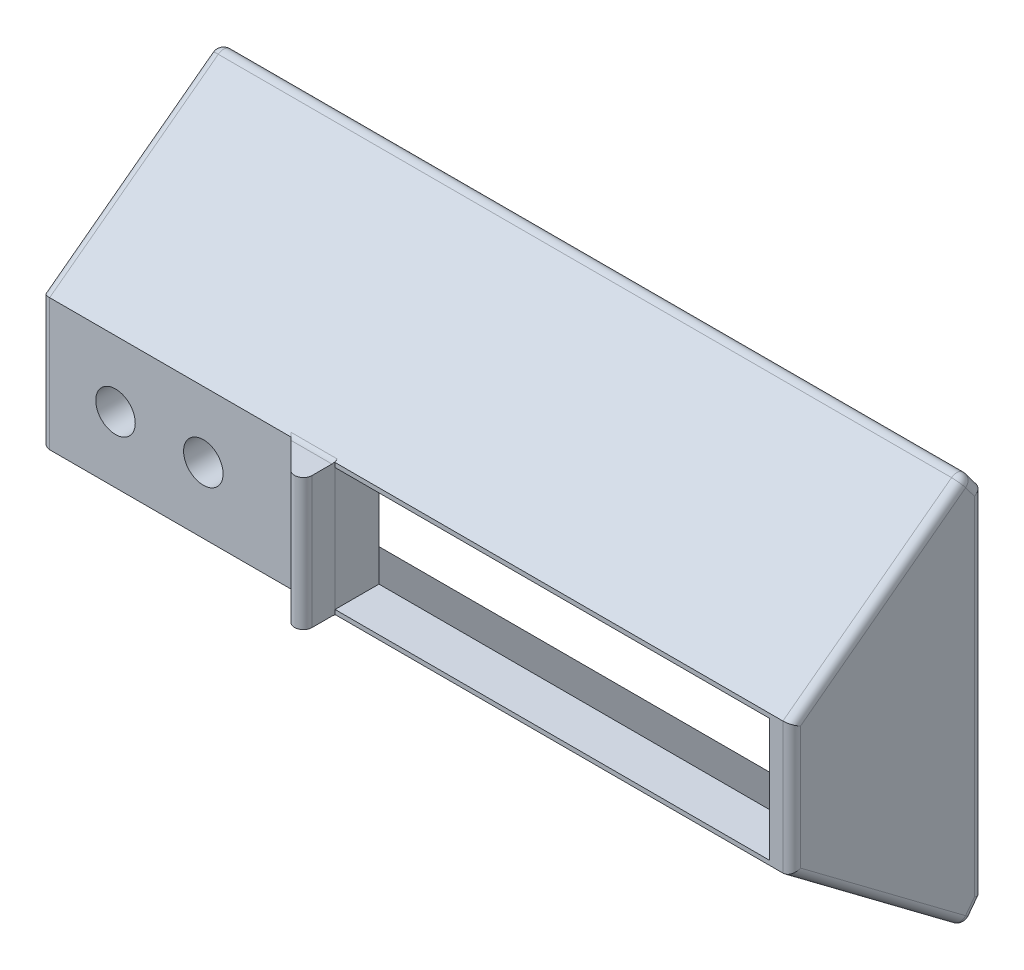
SolidWorks part; units mm, degrees
ref_plane "Front Plane" through (0, 0, 0) normal (1, 0, 0) x (0, 1, 0)
ref_plane "Top Plane" through (0, 0, 0) normal (0, 0, 1) x (0, 1, 0)
ref_plane "Right Plane" through (0, 0, 0) normal (0, 1, 0) x (-1, 0, 0)
sketch "Sketch1" plane through (0, 0, 0) normal (1, 0, 0) x (0, 1, 0)
  line L0 (-7.5, -2.5) -> (-20.1, -19.3)
  line L1 (-7.5, 2.5) -> (7.5, 2.5)
  line L2 (-7.5, 2.5) -> (-7.5, -2.5)
  line L3 (-7.5, -2.5) -> (7.5, -2.5)
  line L4 (7.5, 2.5) -> (7.5, -2.5)
  line L5 (-7.5, 2.5) -> (7.5, -2.5) construction
  line L6 (-7.5, -2.5) -> (7.5, 2.5) construction
  line L7 (-20.1, -19.3) -> (-22.5, -17.5)
  line L8 (-22.5, -17.5) -> (-7.5, 2.5)
  line L9 (0, -2.5) -> (0, 2.5) construction
  line L10 (22.5, -17.5) -> (7.5, 2.5)
  line L11 (20.1, -19.3) -> (22.5, -17.5)
  line L12 (7.5, -2.5) -> (20.1, -19.3)
  point P0 (0, 0)
  point P12 (0, 0)
  dimension "D1" = 20
  dimension "D2" = 15
  dimension "D3" = 5
  dimension "D4" = 15
extrude "Boss-Extrude1" add sketch "Sketch1" along normal blind 80 contours L8 L7 L0 L2 | L4 L1 L2 L3 | L4 L12 L11 L10 region at (0, -14.4174, -9.1507) region at (0, 0, 0) region at (0, 14.4174, -9.1507)
sketch "Sketch2" plane through (0, 0, 2.5) normal (0, 0, 1) x (1, 0, 0)
  line L0 (80, -7.5) -> (80, 7.5) construction
  line L1 (80, 7) -> (30.5, 7)
  line L2 (80, 7) -> (80, -7)
  line L3 (80, -7) -> (30.5, -7)
  line L4 (30.5, 7) -> (30.5, -7)
  line L5 (80, 7) -> (30.5, -7) construction
  line L6 (80, -7) -> (30.5, 7) construction
  line L7 (0, 0) -> (55.25, 0) construction
  line L8 (0, -7.5) -> (0, 7.5) construction
  circle A0 centre (5.5, 0) radius 2.25
  circle A1 centre (15.5, 0) radius 2.25
  point P4 (55.25, 0)
  dimension "D3" = 4.5
  dimension "D1" = 14
  dimension "D2" = 10
  dimension "D4" = 5.5
  dimension "D5" = 15
extrude "Cut-Extrude1" cut sketch "Sketch2" against normal through all
sketch "Sketch3" plane through (0, 0, 2.5) normal (0, 0, 1) x (1, 0, 0)
  line L0 (80, 7.5) -> (0, 7.5) construction
  line L1 (30.4776, 7.5) -> (22.4776, 7.5)
  line L2 (30.4776, 7.5) -> (30.4776, -7.5)
  line L3 (30.4776, -7.5) -> (22.4776, -7.5)
  line L4 (22.4776, 7.5) -> (22.4776, -7.5)
  line L5 (30.4776, 7.5) -> (22.4776, -7.5) construction
  line L6 (30.4776, -7.5) -> (22.4776, 7.5) construction
  line L7 (80, -7.5) -> (0, -7.5) construction
  point P4 (26.4776, 0)
  dimension "D1" = 8
extrude "Boss-Extrude2" add sketch "Sketch3" along normal blind 5
chamfer "Chamfer1" distance 8 angle 45 1 edges at (22.4776, 0, 7.5)
fillet "Fillet1" radius 1 5 edges at (40, -7.5, -2.5) (40, 7.5, -2.5) (27.9776, 7.5, 2.5) (27.9776, -7.5, 2.5) (30.4776, 0, 7.5)
sketch "Sketch4" plane through (0, 0, 0) normal (-1, 0, 0) x (0, -1, 0)
  line L8 (22.5, -17.5) -> (7.5, 2.5)
  line L9 (7.5, 2.5) -> (-7.5, 2.5)
  line L10 (-7.5, 2.5) -> (-22.5, -17.5)
  line L11 (-22.5, -17.5) -> (-20.1, -19.3)
  line L12 (-20.1, -19.3) -> (-7.8, -2.9)
  line L13 (-7, -2.5) -> (7, -2.5)
  line L14 (7.8, -2.9) -> (20.1, -19.3)
  line L15 (20.1, -19.3) -> (22.5, -17.5)
  line L16 (22.5, -17.5) -> (7.5, 2.5)
  line L17 (7.5, 2.5) -> (-7.5, 2.5)
  line L18 (-7.5, 2.5) -> (-22.5, -17.5)
  line L19 (-22.5, -17.5) -> (-20.1, -19.3)
  line L20 (-20.1, -19.3) -> (-7.8, -2.9)
  line L21 (-7, -2.5) -> (7, -2.5)
  line L22 (7.8, -2.9) -> (20.1, -19.3)
  line L23 (20.1, -19.3) -> (22.5, -17.5)
  arc A2 (-7, -2.5) -> (-7.8, -2.9) centre (-7, -3.5) ccw
  arc A3 (7.8, -2.9) -> (7, -2.5) centre (7, -3.5) ccw
  arc A4 (-7, -2.5) -> (-7.8, -2.9) centre (-7, -3.5) ccw
  arc A5 (7.8, -2.9) -> (7, -2.5) centre (7, -3.5) ccw
  dimension "D1" = 0
extrude "Boss-Extrude3" add sketch "Sketch4" along normal blind 3
sketch "Sketch6" plane through (80, 0, 0) normal (1, 0, 0) x (0, 1, 0)
  line L0 (7, 2.5) -> (7, -2.5) construction
  line L1 (7.8, -2.9) -> (20.1, -19.3) construction
  line L2 (20.1, -19.3) -> (22.5, -17.5) construction
  line L3 (22.5, -17.5) -> (7.5, 2.5) construction
  line L4 (7.5, 2.5) -> (7, 2.5) construction
  line L5 (-7, -2.5) -> (-7, 2.5) construction
  line L6 (-7, 2.5) -> (-7.5, 2.5) construction
  line L7 (-7.5, 2.5) -> (-22.5, -17.5) construction
  line L8 (-22.5, -17.5) -> (-20.1, -19.3) construction
  line L9 (-20.1, -19.3) -> (-7.8, -2.9) construction
  line L10 (7, 2.5) -> (7, -2.5)
  line L11 (7.8, -2.9) -> (20.1, -19.3)
  line L12 (20.1, -19.3) -> (22.5, -17.5)
  line L13 (22.5, -17.5) -> (7.5, 2.5)
  line L14 (7.5, 2.5) -> (7, 2.5)
  line L15 (-7, -2.5) -> (-7, 2.5)
  line L16 (-7, 2.5) -> (-7.5, 2.5)
  line L17 (-7.5, 2.5) -> (-22.5, -17.5)
  line L18 (-22.5, -17.5) -> (-20.1, -19.3)
  line L19 (-20.1, -19.3) -> (-7.8, -2.9)
  line L20 (-20.1, -19.3) -> (20.1, -19.3)
  line L21 (-7, 2.5) -> (7, 2.5)
  arc A0 (7.8, -2.9) -> (7, -2.5) centre (7, -3.5) ccw construction
  arc A1 (-7, -2.5) -> (-7.8, -2.9) centre (-7, -3.5) ccw construction
  arc A2 (7.8, -2.9) -> (7, -2.5) centre (7, -3.5) ccw
  arc A3 (-7, -2.5) -> (-7.8, -2.9) centre (-7, -3.5) ccw
  line M1 (7, 2.5) -> (7, -2.5)
  arc M2 (7, -2.5) -> (7.8, -2.9) centre (7, -3.5) cw
  line M3 (7.8, -2.9) -> (20.1, -19.3)
  line M4 (20.1, -19.3) -> (22.5, -17.5)
  line M5 (22.5, -17.5) -> (7.5, 2.5)
  line M6 (7.5, 2.5) -> (7, 2.5)
extrude "Boss-Extrude4" add sketch "Sketch6" along normal blind 2.5 contours L15 A3 L19 L20 L21 M3 M2 M1 | A3 L15 L16 L17 L18 L19 | M6 M1 M2 M3 M4 M5 region at (80, 14.1634, -8.8276) region at (80, 0, -10.582) region at (80, -14.1634, -8.8276)
fillet "Fillet3" radius 1 18 edges at (-3, -13.95, -11.1) (-3, -7.4472, -2.6056) (-3, 0, -2.5) (-3, 7.4472, -2.6056) (-3, 13.95, -11.1) (-3, 21.3, -18.4) (-3, 15, -7.5) (-3, 0, 2.5) (-3, -15, -7.5) (-3, -21.3, -18.4) (82.5, 15, -7.5) (82.5, 21.3, -18.4) (82.5, 0, -19.3) (82.5, -21.3, -18.4) (82.5, -15, -7.5) (82.5, 0, 2.5) (39.75, 22.5, -17.5) (39.75, -22.5, -17.5)
